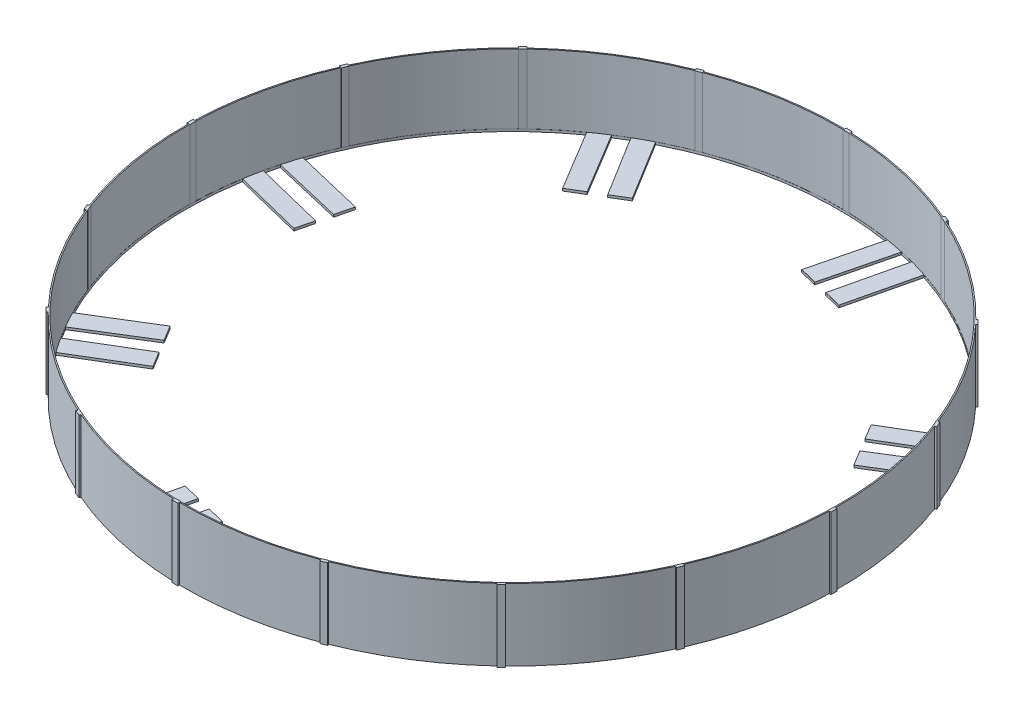
SolidWorks part; units mm, degrees
note: '?' marks a value the reader was unsure of.
ref_plane "Front Plane" through (0, 0, 0) normal (0, 0, 1) x (1, 0, 0)
ref_plane "Top Plane" through (0, 0, 0) normal (0, 1, 0) x (1, 0, 0)
ref_plane "Right Plane" through (0, 0, 0) normal (1, 0, 0) x (0, 0, -1)
sketch "Sketch2" plane through (0, 0, 0) normal (0, 1, 0) x (1, 0, 0)
  circle A0 centre (0, 0) radius 27500
  dimension "D1" = 55000
extrude "Boss-Extrude1" add sketch "Sketch2" along normal blind 6000 contours A0
sketch "Sketch3" plane through (0, 6000, 0) normal (0, 1, 0) x (1, 0, 0)
  circle A0 centre (0, 0) radius 27400
extrude "Cut-Extrude1" cut sketch "Sketch3" against normal blind 5800
ref_plane "Plane1" through (27500, 0, 0) normal (1, 0, 0) x (0, 0, -1)
sketch "Sketch6" plane through (27500, 0, 0) normal (1, 0, 0) x (0, 0, -1)
  line L0 (-387.6781, 6000) -> (-387.6781, 0)
  line L1 (-387.6781, 0) -> (-887.6781, 0)
  line L2 (-887.6781, 0) -> (-887.6781, 6000)
  line L3 (-887.6781, 6000) -> (-387.6781, 6000)
  dimension "D1" = 500
extrude "Boss-Extrude2" add sketch "Sketch6" along normal mid plane 250
pattern_circular "CirPattern1" count 16 over 360 about axis through (-0.0998, 0, -0.0022) along (0, 1, 0) of "Boss-Extrude2"
sketch "Sketch8" plane through (0, 200, 0) normal (0, 1, 0) x (1, 0, 0)
  circle A0 centre (0, 0) radius 27390
extrude "Cut-Extrude2" cut sketch "Sketch8" against normal blind 6227
sketch "Sketch10" plane through (0, 0, 0) normal (0, 1, 0) x (1, 0, 0)
  line L1 (5674.4495, 20624.9369) -> (7130.5937, 20264.8756)
  line L2 (5674.4495, 20624.9369) -> (7045.9309, 26466.0873)
  line L3 (7045.9309, 26466.0873) -> (8525.8905, 26100.3505)
  line L4 (7130.5937, 20264.8756) -> (8525.8905, 26100.3505)
  line L5 (5674.4495, 20624.9369) -> (8525.8905, 26100.3505) construction
  line L6 (7045.9309, 26466.0873) -> (7130.5937, 20264.8756) construction
  line L7 (4448.0345, 27106.7115) -> (5904.4081, 26747.5793)
  line L8 (4448.0345, 27106.7115) -> (2998.731, 21284.3821)
  line L9 (2998.731, 21284.3821) -> (4455.094, 20925.207)
  line L10 (5904.4081, 26747.5793) -> (4455.094, 20925.207)
  line L11 (4448.0345, 27106.7115) -> (4455.094, 20925.207) construction
  line L12 (2998.731, 21284.3821) -> (5904.4081, 26747.5793) construction
  circle A0 centre (0, 0) radius 27390 construction
  point P0 (6597.0321, 23909.272)
  point P9 (4306.9897, 24514.5962)
  dimension "D1" = 6000
  dimension "D2" = 1500
  dimension "D3" = 1500
  dimension "D4" = 5999.9683
  dimension "D5" = 27383.2877
  dimension "D6" = 1500
extrude "Boss-Extrude3" add sketch "Sketch10" along normal blind 200
ref_axis "Axis1" through (0, -877.5, 0) along (0, 1, 0)?
pattern_circular "CirPattern2" count 8 over 360 about axis through (0, 0, 0) along (0, 1, 0) of "Boss-Extrude3"
fillet "Fillet1" radius 20 1 edges at (3726.9125, 200, -21104.7946)
fillet "Fillet2" radius 20 1 edges at (6402.5216, 200, -20444.9063)
